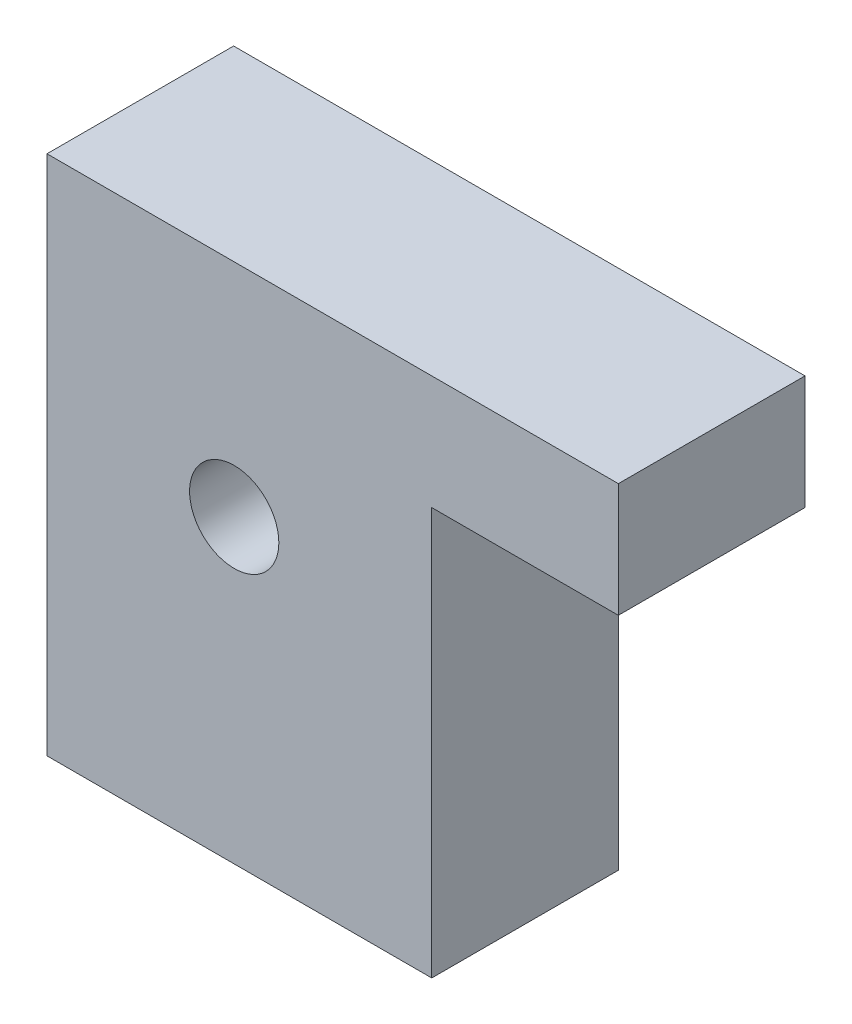
SolidWorks part; units mm, degrees
ref_plane "Ebene vorne" through (0, 0, 0) normal (0, 0, 1) x (1, 0, 0)
ref_plane "Ebene oben" through (0, 0, 0) normal (0, 1, 0) x (1, 0, 0)
ref_plane "Ebene rechts" through (0, 0, 0) normal (1, 0, 0) x (0, 0, -1)
sketch "Skizze1" plane through (0, 0, 0) normal (0, 0, 1) x (1, 0, 0)
  line L1 (0, 0) -> (20.6158, 0)
  line L2 (0, 0) -> (0, -27.9399)
  line L3 (0, -27.9399) -> (20.6158, -27.9399)
  line L4 (20.6158, 0) -> (20.6158, -27.9399)
extrude "Aufsatz-Linear austragen1" add sketch "Skizze1" along normal blind 10
sketch "Skizze2" plane through (0, 0, 10) normal (0, 0, 1) x (1, 0, 0)
  circle A0 centre (10.0314, -11.8384) radius 2.3913
sketch "Skizze3" plane through (20.6158, 0, 0) normal (1, 0, 0) x (0, 0, -1)
  line L0 (0, -27.9399) -> (0, 0) construction
  line L1 (-10, 0) -> (0, 0)
  line L2 (-10, 0) -> (-10, -6.1104)
  line L3 (-10, -6.1104) -> (0, -6.1104)
  line L4 (0, 0) -> (0, -6.1104)
extrude "Aufsatz-Linear austragen2" add sketch "Skizze3" along normal blind 10
extrude "Schnitt-Linear austragen1" cut sketch "Skizze2" against normal blind 10 contours A0
